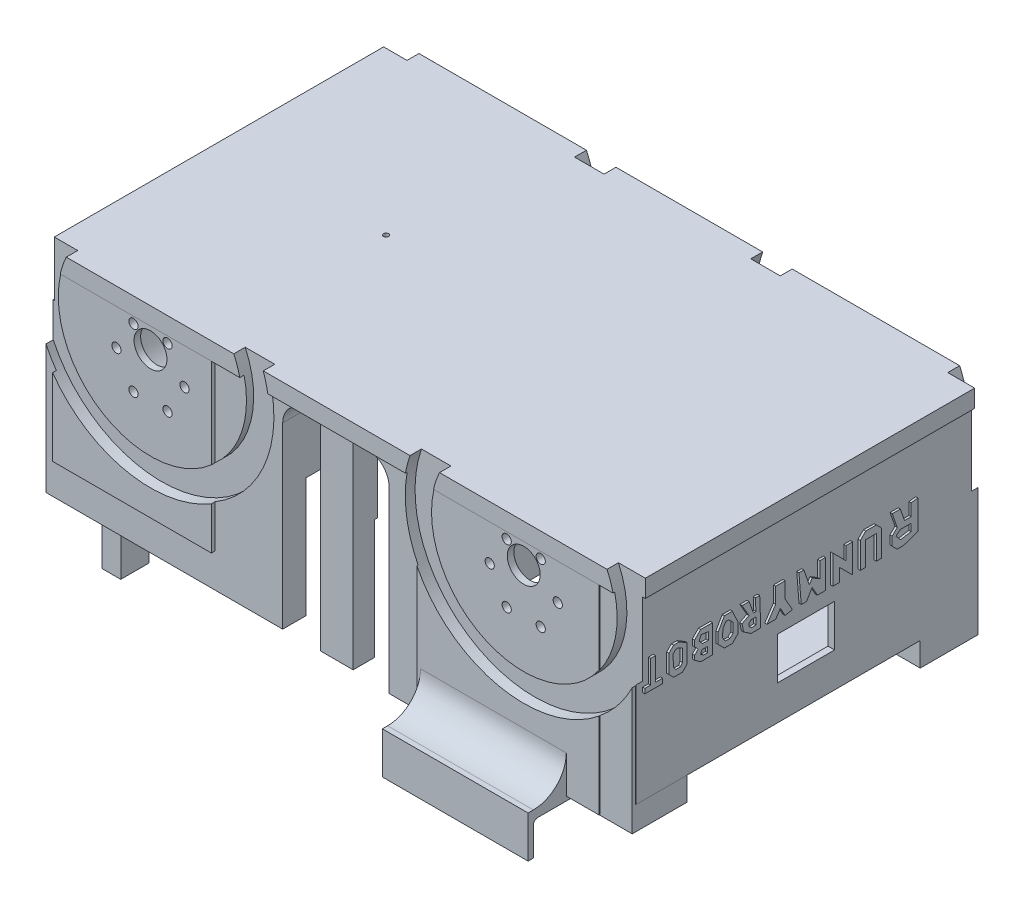
SolidWorks part; units mm, degrees
ref_plane "Front Plane" through (0, 0, 0) normal (0, 0, 1) x (1, 0, 0)
ref_plane "Top Plane" through (0, 0, 0) normal (0, 1, 0) x (1, 0, 0)
ref_plane "Right Plane" through (0, 0, 0) normal (1, 0, 0) x (0, 0, -1)
sketch "MotorHoldersSketch" plane through (0, 0, 0) normal (0, 0, 1) x (1, 0, 0)
  line L0 (0, 0) -> (170, 0) construction
  line L1 (0, 0) -> (0, 23.41) construction
  line L2 (170, 0) -> (170, 23.41) construction
  circle A0 centre (0, 0) radius 23.41
  circle A1 centre (170, 0) radius 23.41
ref_axis "MotorCenterAxis1" through (0, 0, 0) along (0, 0, 1)
ref_axis "MotorCenterAxis2" through (170, 0, 0) along (0, 0, 1)
extrude "MotorHolders" add sketch "MotorHoldersSketch" along normal blind 80 and the other way blind 80
sketch "Sketch3" plane through (0, 0, 0) normal (0, 0, 1) x (1, 0, 0)
  line L1 (1.9406, 21.133) -> (168.3435, 21.133)
  line L2 (1.9406, 21.133) -> (1.9406, 18.3155)
  line L3 (1.9406, 18.3155) -> (168.3435, 18.3155)
  line L4 (168.3435, 21.133) -> (168.3435, 18.3155)
sketch "Sketch4" plane through (0, 0, 0) normal (0, 1, 0) x (1, 0, 0)
  line L1 (221.2811, -76.3794) -> (-41.4939, -76.3794)
  line L2 (221.2811, -76.3794) -> (221.2811, 76.7331)
  line L3 (221.2811, 76.7331) -> (-41.4939, 76.7331)
  line L4 (-41.4939, -76.3794) -> (-41.4939, 76.7331)
extrude "Cut-Extrude1" cut sketch "Sketch4" against normal blind 26
ref_axis "Axis3" through (170, 0, 0) along (0, -1, 0)
sketch3d "ReferencePlanePosition"
  line L0 (170, 0, 0) -> (170, -34.8293, 0)
  line L1 (170, 0, 0) -> (170, -38.994, 0) construction
ref_plane "ReferencePlane" through (170, -34.8293, 0) normal (0, -1, 0) x (-1, 0, 0)
sketch "Sketch6" plane through (170, -34.8293, 0) normal (0, -1, 0) x (-1, 0, 0)
  line L1 (219.5858, 78.949) -> (112.1002, 78.949)
  line L2 (219.5858, 78.949) -> (219.5858, 65.5282)
  line L3 (219.5858, 65.5282) -> (112.1002, 65.5282)
  line L4 (112.1002, 78.949) -> (112.1002, 65.5282)
  line L5 (219.3147, -40.0209) -> (111.499, -40.0209)
  line L6 (219.3147, -40.0209) -> (219.3147, -78.2822)
  line L7 (219.3147, -78.2822) -> (111.499, -78.2822)
  line L8 (111.499, -40.0209) -> (111.499, -78.2822)
  line L9 (61.4891, 77.8627) -> (19.9904, 77.8627)
  line L10 (61.4891, 77.8627) -> (61.4891, 40.7512)
  line L11 (61.4891, 40.7512) -> (19.9904, 40.7512)
  line L12 (19.9904, 77.8627) -> (19.9904, 40.7512)
  line L13 (61.8484, -44.1716) -> (20.0852, -44.1716)
  line L14 (61.8484, -44.1716) -> (61.8484, -79.4437)
  line L15 (61.8484, -79.4437) -> (20.0852, -79.4437)
  line L16 (20.0852, -44.1716) -> (20.0852, -79.4437)
  line L17 (213.765, 73.0364) -> (192.9548, 73.0364)
  line L18 (213.765, 73.0364) -> (213.765, 71.0153)
  line L19 (213.765, 71.0153) -> (192.9548, 71.0153)
  line L20 (192.9548, 73.0364) -> (192.9548, 71.0153)
  line L21 (41.3552, 69.1777) -> (28.5109, 69.1777)
  line L22 (41.3552, 69.1777) -> (41.3552, 50.8413)
  line L23 (41.3552, 50.8413) -> (28.5109, 50.8413)
  line L24 (28.5109, 69.1777) -> (28.5109, 50.8413)
  line L25 (43.3068, -72.8101) -> (32.1723, -72.8101)
  line L26 (43.3068, -72.8101) -> (43.3068, -54.7747)
  line L27 (43.3068, -54.7747) -> (32.1723, -54.7747)
  line L28 (32.1723, -72.8101) -> (32.1723, -54.7747)
  line L29 (211.9411, -70.4881) -> (201.0982, -70.4881)
  line L30 (211.9411, -70.4881) -> (211.9411, -60.1404)
  line L31 (211.9411, -60.1404) -> (201.0982, -60.1404)
  line L32 (201.0982, -70.4881) -> (201.0982, -60.1404)
  line L33 (97.1795, 78.949) -> (79.4162, 78.949)
  line L34 (97.1795, 78.949) -> (97.1795, 67.7632)
  line L35 (97.1795, 67.7632) -> (79.4162, 67.7632)
  line L36 (79.4162, 78.949) -> (79.4162, 67.7632)
  line L37 (58.6711, 51.3198) -> (53.8697, 51.3198)
  line L38 (58.6711, 51.3198) -> (58.6711, 67.7632)
  line L39 (58.6711, 67.7632) -> (53.8697, 67.7632)
  line L40 (53.8697, 51.3198) -> (53.8697, 67.7632)
  line L41 (94.2281, -78.2822) -> (79.4162, -78.2822)
  line L42 (94.2281, -78.2822) -> (94.2281, -67.2515)
  line L43 (94.2281, -67.2515) -> (79.4162, -67.2515)
  line L44 (79.4162, -78.2822) -> (79.4162, -67.2515)
  line L45 (56.3648, -69.8638) -> (51.7107, -69.8638)
  line L46 (56.3648, -69.8638) -> (56.3648, -55.4273)
  line L47 (56.3648, -55.4273) -> (51.7107, -55.4273)
  line L48 (51.7107, -69.8638) -> (51.7107, -55.4273)
  line L49 (-20.7001, -79.4437) -> (-48.8506, -79.4437)
  line L50 (-20.7001, -79.4437) -> (-20.7001, -54.5097)
  line L51 (-20.7001, -54.5097) -> (-48.8506, -54.5097)
  line L52 (-48.8506, -79.4437) -> (-48.8506, -54.5097)
  line L53 (-18.3873, 77.8627) -> (-49.0581, 77.8627)
  line L54 (-18.3873, 77.8627) -> (-18.3873, 51.5325)
  line L55 (-18.3873, 51.5325) -> (-49.0581, 51.5325)
  line L56 (-49.0581, 77.8627) -> (-49.0581, 51.5325)
  line L57 (-41.8141, -72.8101) -> (-31.6362, -72.8101)
  line L58 (-41.8141, -72.8101) -> (-41.8141, -62.9794)
  line L59 (-41.8141, -62.9794) -> (-31.6362, -62.9794)
  line L60 (-31.6362, -72.8101) -> (-31.6362, -62.9794)
  line L61 (-31.6362, 69.1777) -> (-41.5347, 69.1777)
  line L62 (-31.6362, 69.1777) -> (-31.6362, 58.5421)
  line L63 (-31.6362, 58.5421) -> (-41.5347, 58.5421)
  line L64 (-41.5347, 69.1777) -> (-41.5347, 58.5421)
extrude "PowerBankHolders" add sketch "Sketch6" along normal blind 40 and the other way blind 59 separate body
sketch3d "3DSketch3"
  line L0 (170, 0, 0) -> (170, -64.5, 0) construction
ref_plane "Plane2" through (170, -64.5, 0) normal (0, -1, 0) x (-1, 0, 0)
sketch "Sketch7" plane through (170, -64.5, 0) normal (0, -1, 0) x (-1, 0, 0)
  line L1 (-9.5047, -80.801) -> (181.32, -80.801)
  line L2 (-9.5047, -80.801) -> (-9.5047, 73.8662)
  line L3 (-9.5047, 73.8662) -> (181.32, 73.8662)
  line L4 (181.32, -80.801) -> (181.32, 73.8662)
  line L5 (151.8712, -54.3972) -> (26.5361, -54.3972)
  line L6 (151.8712, -54.3972) -> (151.8712, 46.2413)
  line L7 (151.8712, 46.2413) -> (26.5361, 46.2413)
  line L8 (26.5361, -54.3972) -> (26.5361, 46.2413)
ref_point "Point1"
ref_point "Point2"
sketch3d "3DSketch11"
  line L0 (0, 0, -80) -> (170, 0, 80) construction
  point P4 (85, 0, 0)
sketch "MotorHolderExtrudeSketch" plane through (0, 0, 0) normal (0, 0, 1) x (1, 0, 0)
  circle A0 centre (170, 0) radius 20.415
  circle A1 centre (0, 0) radius 20.415
  circle A3 centre (0, 0) radius 23.41 construction
  circle A4 centre (170, 0) radius 23.41 construction
ref_point "TopOfMotors"
ref_plane "TangentToTopOfMotors" through (0, -20.415, 0) normal (0, 1, 0) x (1, 0, 0)
ref_axis "Axis4" through (85, 0, 0) along (0, -1, 0)
ref_plane "BottomOfPowerBankRegion" through (0, -20.425, 0) normal (0, 1, 0) x (1, 0, 0)
ref_point "CenterAtBottomOfPowerBank"
ref_plane "TopOfPowerBankPlane" through (0, -54.425, 0) normal (0, 1, 0) x (1, 0, 0)
sketch "Sketch13" plane through (0, -54.425, 0) normal (0, 1, 0) x (1, 0, 0)
  line L1 (-19.4498, 72.5454) -> (166.1636, 72.5454)
  line L2 (-19.4498, 72.5454) -> (-19.4498, -78.2051)
  line L3 (-19.4498, -78.2051) -> (166.1636, -78.2051)
  line L4 (166.1636, 72.5454) -> (166.1636, -78.2051)
  line L5 (19.3173, -49.583) -> (137.9607, -49.583)
  line L6 (19.3173, -49.583) -> (19.3173, -21.0549)
  line L7 (19.3173, -21.0549) -> (137.9607, -21.0549)
  line L8 (137.9607, -49.583) -> (137.9607, -21.0549)
  line L9 (19.3173, 56.6778) -> (137.9607, 56.6778)
  line L10 (19.3173, 56.6778) -> (19.3173, 36.3234)
  line L11 (19.3173, 36.3234) -> (137.9607, 36.3234)
  line L12 (137.9607, 56.6778) -> (137.9607, 36.3234)
  line L13 (19.3173, 18.3186) -> (137.9607, 18.3186)
  line L14 (19.3173, 18.3186) -> (19.3173, -7.3615)
  line L15 (19.3173, -7.3615) -> (137.9607, -7.3615)
  line L16 (137.9607, 18.3186) -> (137.9607, -7.3615)
sketch "Sketch15" plane through (150.0096, 0, 0) normal (1, 0, 0) x (0, 0, -1)
  line L1 (72.5313, -25.7765) -> (45.7099, -25.7765)
  line L2 (72.5313, -25.7765) -> (72.5313, -24.2242)
  line L3 (72.5313, -24.2242) -> (45.7099, -24.2242)
  line L4 (45.7099, -25.7765) -> (45.7099, -24.2242)
ref_plane "Plane6" through (0, 0, 0) normal (0, 0, 1) x (1, 0, 0)
sketch "MotorGeometry1" plane through (0, 0, 0) normal (0, 0, 1) x (1, 0, 0)
  line L0 (170, 0) -> (170, -13.42)
  line L1 (170, 0) -> (170, -34.8293) construction
  line L2 (170, -13.42) -> (162.25, -13.42) construction
  line L3 (170, -13.42) -> (177.75, -13.42) construction
  line L4 (170, -13.42) -> (170, 7) construction
  line L5 (170, 0) -> (185.5, 0) construction
  line L6 (170, 0) -> (154.5, 0) construction
  line L7 (170, 0) -> (170, 13.42) construction
  line L8 (170, 0) -> (170, 23.41) construction
  line L9 (170, 13.42) -> (177.75, 13.42) construction
  line L10 (170, 13.42) -> (162.25, 13.42)
ref_axis "BoltAxisA" through (185.5, 0, 0) along (0, 0, 1)
ref_axis "BoltAxisB" through (177.75, -13.42, 0) along (0, 0, 1)
ref_axis "BoltAxisC" through (162.25, -13.42, 0) along (0, 0, 1)
ref_axis "BoltAxisD" through (154.5, 0, 0) along (0, 0, 1)
ref_axis "BoltAxisE" through (162.25, 13.42, 0) along (0, 0, 1)
ref_axis "BoltAxisF" through (177.75, 13.42, 0) along (0, 0, 1)
ref_point "Point6"
ref_point "Point7"
ref_point "Point8"
ref_point "Point9"
ref_point "Point10"
ref_point "Point11"
ref_point "Point12"
ref_point "Point13"
ref_point "Point14"
ref_point "Point15"
ref_point "Point16"
ref_point "Point17"
ref_plane "Plane7" through (0, 0, 0) normal (0, 0, 1) x (1, 0, 0)
sketch "MotorGeometry2" plane through (0, 0, 0) normal (0, 0, 1) x (1, 0, 0)
  line L0 (0, 0) -> (0, -13.42) construction
  line L1 (0, -13.42) -> (7.75, -13.42) construction
  line L2 (0, -13.42) -> (-7.75, -13.42) construction
  line L3 (0, 0) -> (0, 13.42)
  line L4 (0, -13.42) -> (0, 7) construction
  line L5 (0, 13.42) -> (7.75, 13.42) construction
  line L6 (0, 13.42) -> (-7.75, 13.42) construction
  line L7 (0, 0) -> (15.5, 0) construction
  line L8 (0, 0) -> (-15.5, 0) construction
  line L9 (0, 0) -> (0, 23.41) construction
ref_axis "Axis11" through (15.5, 0, 0) along (0, 0, 1)
ref_axis "Axis12" through (7.75, 13.42, 0) along (0, 0, 1)
ref_axis "Axis13" through (-7.75, 13.42, 0) along (0, 0, 1)
ref_axis "Axis14" through (-15.5, 0, 0) along (0, 0, 1)
ref_axis "Axis15" through (-7.75, -13.42, 0) along (0, 0, 1)
ref_axis "Axis16" through (7.75, -13.42, 0) along (0, 0, 1)
ref_point "Point18"
ref_point "Point19"
ref_point "Point20"
ref_point "Point21"
ref_point "Point22"
ref_point "Point23"
ref_point "Point24"
ref_point "Point25"
ref_point "Point26"
ref_point "Point27"
ref_point "Point28"
ref_point "Point29"
ref_plane "BottomPlane" through (0, 19.575, 0) normal (0, 1, 0) x (1, 0, 0)
ref_axis "OutputShaftReference1" through (0, 7, 0) along (0, 0, 1)
ref_point "Point35"
ref_axis "OutputShaftReference2" through (170, 7, 0) along (0, 0, 1)
sketch "Sketch21" plane through (0, 19.575, 0) normal (0, 1, 0) x (1, 0, 0)
  line L0 (219.6842, -79.5488) -> (-50.341, -79.5488) construction
  line L1 (-50.341, -79.5488) -> (-50.341, 79.7899) construction
  line L2 (-50.341, 79.7899) -> (219.6842, 79.7899) construction
  line L3 (219.6842, 79.7899) -> (219.6842, -79.5488) construction
  circle A0 centre (85, 0) radius 156.3953
extrude "BottomPlate" add sketch "Sketch21" along normal blind 5 and the other way blind 3
ref_plane "HoleReferencePlane1" through (0, 0, 80) normal (0, 0, 1) x (1, 0, 0)
ref_point "OutputShaftPosition3"
ref_point "OutputShaftPosition1"
sketch "Sketch23" plane through (0, 0, 80) normal (0, 0, 1) x (1, 0, 0)
  line L1 (27.7411, -59.3229) -> (-44.5901, -59.3229)
  line L2 (27.7411, -59.3229) -> (27.7411, 21.8402)
  line L3 (27.7411, 21.8402) -> (-44.5901, 21.8402)
  line L4 (-44.5901, -59.3229) -> (-44.5901, 21.8402)
  line L5 (121.3218, 21.8402) -> (204.258, 21.8402)
  line L6 (121.3218, 21.8402) -> (121.3218, -74.371)
  line L7 (121.3218, -74.371) -> (204.258, -74.371)
  line L8 (204.258, 21.8402) -> (204.258, -74.371)
extrude "MotorMountingSupport1" add sketch "Sketch23" against normal blind 6
ref_plane "HoleReferencePlane2" through (0, 0, -80) normal (0, 0, -1) x (-1, 0, 0)
ref_point "OutputShaftPosition4"
ref_point "OutputShaftPosition2"
sketch "Sketch24" plane through (0, 0, -80) normal (0, 0, -1) x (-1, 0, 0)
  line L1 (-202.1905, -75.2023) -> (-123.8485, -75.2023)
  line L2 (-202.1905, -75.2023) -> (-202.1905, 19.2374)
  line L3 (-202.1905, 19.2374) -> (-123.8485, 19.2374)
  line L4 (-123.8485, -75.2023) -> (-123.8485, 19.2374)
  line L5 (-24.3642, -64.1521) -> (29.5505, -64.1521)
  line L6 (-24.3642, -64.1521) -> (-24.3642, 22.5226)
  line L7 (-24.3642, 22.5226) -> (29.5505, 22.5226)
  line L8 (29.5505, -64.1521) -> (29.5505, 22.5226)
extrude "MotorMountingSuppor2" add sketch "Sketch24" against normal blind 6
sketch "Sketch17" plane through (0, 0, 80) normal (0, 0, 1) x (1, 0, 0)
  circle A0 centre (185.5, 0) radius 2.1
  circle A1 centre (177.75, -13.42) radius 2.1
  circle A2 centre (162.25, -13.42) radius 2.1
  circle A3 centre (154.5, 0) radius 2.1
  circle A4 centre (162.25, 13.42) radius 2.1
  circle A5 centre (177.75, 13.42) radius 2.1
  circle A6 centre (170, 7) radius 7.5
extrude "MotorHoles1" cut sketch "Sketch17" against normal blind 31.5
sketch "Sketch19" plane through (0, 0, -80) normal (0, 0, -1) x (-1, 0, 0)
  circle A0 centre (-185.5, 0) radius 2.1
  circle A1 centre (-177.75, -13.42) radius 2.1
  circle A2 centre (-162.25, -13.42) radius 2.1
  circle A3 centre (-154.5, 0) radius 2.1
  circle A4 centre (-162.25, 13.42) radius 2.1
  circle A5 centre (-177.75, 13.42) radius 2.1
  circle A6 centre (-170, 7) radius 7.5
sketch "BoltHolesSketch3" plane through (0, 0, 80) normal (0, 0, 1) x (1, 0, 0)
  circle A0 centre (7.75, -13.42) radius 2.1
  circle A1 centre (15.5, 0) radius 2.1
  circle A2 centre (7.75, 13.42) radius 2.1
  circle A3 centre (-7.75, 13.42) radius 2.1
  circle A4 centre (-15.5, 0) radius 2.1
  circle A5 centre (-7.75, -13.42) radius 2.1
  circle A6 centre (0, 7) radius 7.5
extrude "Cut-Extrude4" cut sketch "Sketch19" against normal blind 30
extrude "MotorHoles3" cut sketch "BoltHolesSketch3" against normal blind 31.5
sketch "BoltHolesSketch4" plane through (0, 0, -80) normal (0, 0, -1) x (-1, 0, 0)
  circle A0 centre (-15.5, 0) radius 2.1
  circle A1 centre (-7.75, 13.42) radius 2.1
  circle A2 centre (7.75, 13.42) radius 2.1
  circle A3 centre (15.5, 0) radius 2.1
  circle A4 centre (7.75, -13.42) radius 2.1
  circle A5 centre (-7.75, -13.42) radius 2.1
  circle A6 centre (0, 7) radius 7.5
extrude "MotorHoles4" cut sketch "BoltHolesSketch4" against normal blind 15
ref_plane "Front" through (219.0581, 0, 0) normal (1, 0, 0) x (0, 0, -1)
sketch "Sketch29" plane through (219.0581, 0, 0) normal (1, 0, 0) x (0, 0, -1)
  line L1 (76.6955, -63.9254) -> (-77.9397, -63.9254)
  line L2 (76.6955, -63.9254) -> (76.6955, 20.2062)
  line L3 (76.6955, 20.2062) -> (-77.9397, 20.2062)
  line L4 (-77.9397, -63.9254) -> (-77.9397, 20.2062)
  line L5 (-13.4507, -48.1531) -> (12.5493, -48.1531)
  line L6 (-13.4507, -48.1531) -> (-13.4507, -28.9404)
  line L7 (-13.4507, -28.9404) -> (12.5493, -28.9404)
  line L8 (12.5493, -48.1531) -> (12.5493, -28.9404)
extrude "Boss-Extrude8" add sketch "Sketch29" against normal blind 3
ref_plane "RaspberryPiBasePlane" through (0, 16.575, 0) normal (0, -1, 0) x (-1, 0, 0)
sketch "Sketch27" plane through (0, 16.575, 0) normal (0, -1, 0) x (-1, 0, 0)
  line L1 (31.6337, 64.5517) -> (-194.8264, 64.5517)
  line L2 (31.6337, 64.5517) -> (31.6337, -65.4335)
  line L3 (31.6337, -65.4335) -> (-194.8264, -65.4335)
  line L4 (-194.8264, 64.5517) -> (-194.8264, -65.4335)
extrude "Boss-Extrude6" add sketch "Sketch27" against normal blind 3
ref_plane "Plane12" through (0, -74.8293, 0) normal (0, -1, 0) x (-1, 0, 0)
sketch "Sketch28" plane through (0, -74.8293, 0) normal (0, -1, 0) x (-1, 0, 0)
  line L1 (-189.3897, -97.3973) -> (-123.0026, -97.3973)
  line L2 (-189.3897, -97.3973) -> (-189.3897, 96.7192)
  line L3 (-189.3897, 96.7192) -> (-123.0026, 96.7192)
  line L4 (-123.0026, -97.3973) -> (-123.0026, 96.7192)
extrude "CellPhonePlate" add sketch "Sketch28" along normal blind 1.5 and the other way blind 2.5
sketch "Sketch40" plane through (0, 16.575, 0) normal (0, -1, 0) x (1, 0, 0)
  line L1 (-49.5858, -65.5282) -> (-15.7443, -65.5282)
  line L2 (-49.5858, -65.5282) -> (-49.5858, -33.9964)
  line L3 (-49.5858, -33.9964) -> (-15.7443, -33.9964)
  line L4 (-15.7443, -65.5282) -> (-15.7443, -33.9964)
extrude "Boss-Extrude11" add sketch "Sketch40" along normal blind 40
fillet "Fillet2" radius 15 1 edges at (-33.0588, 16.575, -33.9964) type face fillet first side face at (-28.7089, -2.1691, -33.9964) second side face at (85, 16.575, 156.3953)
fillet "Fillet3" radius 15 1 edges at (-32.6651, -23.425, -65.5282) type face fillet first side face at (-5.65, -13.42, -65.5282) second side face at (-32.6651, -23.425, -49.7623)
sketch "Sketch11" plane through (0, -20.425, 0) normal (0, 1, 0) x (1, 0, 0)
  line L0 (-34.2162, 4.2922) -> (204.2162, -4.2922) construction
  line L5 (-34.2162, -64.7581) -> (-34.2162, 73.3425)
  line L6 (204.2162, 63.611) -> (204.2162, -72.1954)
  line L7 (204.2162, -72.1954) -> (-34.2162, -64.7581)
  line L8 (204.2162, 63.611) -> (-34.2162, 73.3425)
  circle A0 centre (85, 0) radius 104 construction
extrude "PowerBankCut" cut sketch "Sketch11" against normal up to surface (54.4043 mm away) up to face at (204.7754, -74.8293, 66.9767)
extrude "MotorHolderCut" cut sketch "MotorHolderExtrudeSketch" against normal blind 77 and the other way blind 77
sketch "Sketch31" plane through (219.0581, 0, 0) normal (1, 0, 0) x (0, 0, -1)
  line L0 (49.4417, -6.1927) -> (49.4417, -19.3739)
  line L1 (49.4417, -19.3739) -> (42.9342, -21.6341)
  line L2 (42.9342, -21.6341) -> (40.0618, -21.6341)
  line L3 (40.0618, -21.6341) -> (37.7863, -19.3586)
  line L4 (37.7863, -19.3586) -> (37.7863, -15.3813)
  line L5 (37.7863, -15.3813) -> (40.0618, -13.1059)
  line L6 (40.0618, -13.1059) -> (37.7863, -6.5545)
  line L7 (37.7863, -6.5545) -> (41.498, -6.5545)
  line L8 (41.498, -6.5545) -> (43.4004, -12.0319)
  line L9 (43.4004, -12.0319) -> (46.389, -12.0319)
  line L10 (46.389, -12.0319) -> (46.389, -6.5545)
  line L11 (46.389, -6.5545) -> (49.4417, -6.1927)
  line L12 (33.0193, -21.6341) -> (33.0193, -9.8302)
  line L13 (33.0193, -9.8302) -> (30.5402, -7.3511)
  line L14 (30.5402, -7.3511) -> (25.7203, -7.3511)
  line L15 (25.7203, -7.3511) -> (23.2412, -9.8302)
  line L16 (23.2412, -9.8302) -> (23.2412, -21.6341)
  line L17 (23.2412, -21.6341) -> (25.7203, -21.6341)
  line L18 (25.7203, -21.6341) -> (25.7203, -10.7454)
  line L19 (25.7203, -10.7454) -> (30.5402, -10.7454)
  line L20 (30.5402, -10.7454) -> (30.5402, -21.6341)
  line L21 (30.5402, -21.6341) -> (33.0193, -21.6341)
  line L22 (19.7226, -8.5907) -> (19.7226, -21.6341)
  line L23 (19.7226, -21.6341) -> (13.8207, -15.7322)
  line L24 (13.8207, -15.7322) -> (13.8207, -21.6341)
  line L25 (13.8207, -21.6341) -> (10.7708, -21.6341)
  line L26 (10.7708, -21.6341) -> (10.7708, -8.5907)
  line L27 (10.7708, -8.5907) -> (16.7716, -14.5915)
  line L28 (16.7716, -14.5915) -> (16.7716, -8.5907)
  line L29 (16.7716, -8.5907) -> (19.7226, -8.5907)
  line L30 (7.3891, -8.5907) -> (7.3891, -21.6341)
  line L31 (7.3891, -21.6341) -> (3.7282, -21.6341)
  line L32 (3.7282, -21.6341) -> (1.3209, -17.37)
  line L33 (1.3209, -17.37) -> (-1.2519, -21.6341)
  line L34 (-1.2519, -21.6341) -> (-3.6554, -21.6341)
  line L35 (-3.6554, -21.6341) -> (-4.6916, -8.5907)
  line L36 (-4.6916, -8.5907) -> (-2.4537, -8.5907)
  line L37 (-2.4537, -8.5907) -> (0.0345, -15.7545)
  line L38 (0.0345, -15.7545) -> (1.3209, -13.6224)
  line L39 (1.3209, -13.6224) -> (4.8544, -15.7545)
  line L40 (4.8544, -15.7545) -> (4.8544, -8.5907)
  line L41 (4.8544, -8.5907) -> (7.3891, -8.5907)
  line L42 (-7.6823, -21.6341) -> (-10.9875, -15.7545)
  line L43 (-10.9875, -15.7545) -> (-10.9875, -8.5907)
  line L44 (-10.9875, -8.5907) -> (-15.3102, -8.5907)
  line L45 (-15.3102, -8.5907) -> (-15.3102, -15.7545)
  line L46 (-15.3102, -15.7545) -> (-19.2695, -21.6341)
  line L47 (-19.2695, -21.6341) -> (-15.3102, -21.6341)
  line L48 (-15.3102, -21.6341) -> (-13.1489, -18.4245)
  line L49 (-13.1489, -18.4245) -> (-10.9875, -22.2693)
  line L50 (-10.9875, -22.2693) -> (-7.6823, -21.6341)
  line L51 (46.389, -17.8857) -> (46.389, -14.5915)
  line L52 (46.389, -14.5915) -> (41.498, -14.5915)
  line L53 (41.498, -14.5915) -> (39.5067, -16.2541)
  line L54 (39.5067, -16.2541) -> (41.5656, -18.7201)
  line L55 (41.5656, -18.7201) -> (46.389, -17.8857)
  line L56 (-22.571, -8.5907) -> (-22.0989, -21.6341)
  line L57 (-22.0989, -21.6341) -> (-26.4915, -21.6341)
  line L58 (-26.4915, -21.6341) -> (-29.9116, -19.3586)
  line L59 (-29.9116, -19.3586) -> (-30.636, -15.7545)
  line L60 (-30.636, -15.7545) -> (-27.4135, -14.1052)
  line L61 (-27.4135, -14.1052) -> (-30.636, -8.5907)
  line L62 (-30.636, -8.5907) -> (-27.4135, -8.5907)
  line L63 (-27.4135, -8.5907) -> (-25.3987, -14.1052)
  line L64 (-25.3987, -14.1052) -> (-24.2952, -14.1052)
  line L65 (-24.2952, -14.1052) -> (-24.4948, -8.5907)
  line L66 (-24.4948, -8.5907) -> (-22.571, -8.5907)
  line L67 (-35.0099, -8.5907) -> (-38.6395, -8.5907)
  line L68 (-38.6395, -8.5907) -> (-41.5241, -13.6224)
  line L69 (-41.5241, -13.6224) -> (-41.5241, -18.4245)
  line L70 (-41.5241, -18.4245) -> (-38.6395, -21.3091)
  line L71 (-38.6395, -21.3091) -> (-35.0099, -21.3091)
  line L72 (-35.0099, -21.3091) -> (-32.4978, -18.797)
  line L73 (-32.4978, -18.797) -> (-32.4978, -14.1052)
  line L74 (-32.4978, -14.1052) -> (-35.0099, -8.5907)
  line L75 (-44.0593, -21.3091) -> (-44.0593, -8.5907)
  line L76 (-44.0593, -8.5907) -> (-49.4499, -8.5907)
  line L77 (-49.4499, -8.5907) -> (-52.2269, -11.3677)
  line L78 (-52.2269, -11.3677) -> (-52.2269, -14.1052)
  line L79 (-52.2269, -14.1052) -> (-50.5777, -15.7545)
  line L80 (-50.5777, -15.7545) -> (-52.2269, -17.4037)
  line L81 (-52.2269, -17.4037) -> (-52.2269, -19.3586)
  line L82 (-52.2269, -19.3586) -> (-49.4499, -21.3091)
  line L83 (-49.4499, -21.3091) -> (-44.0593, -21.3091)
  line L84 (-57.7977, -21.3091) -> (-55.6011, -19.1125)
  line L85 (-55.6011, -19.1125) -> (-55.6011, -10.7454)
  line L86 (-55.6011, -10.7454) -> (-59.2637, -8.5907)
  line L87 (-59.2637, -8.5907) -> (-61.7818, -8.5907)
  line L88 (-61.7818, -8.5907) -> (-63.9365, -10.7454)
  line L89 (-63.9365, -10.7454) -> (-63.9365, -19.1125)
  line L90 (-63.9365, -19.1125) -> (-61.7818, -21.2672)
  line L91 (-61.7818, -21.2672) -> (-57.7977, -21.3091)
  line L92 (-66.7918, -21.2672) -> (-74.8705, -21.2672)
  line L93 (-74.8705, -21.2672) -> (-74.8705, -19.1125)
  line L94 (-74.8705, -19.1125) -> (-72.2665, -19.1125)
  line L95 (-72.2665, -19.1125) -> (-72.2665, -8.5907)
  line L96 (-72.2665, -8.5907) -> (-69.9977, -8.5907)
  line L97 (-69.9977, -8.5907) -> (-69.9977, -19.1125)
  line L98 (-69.9977, -19.1125) -> (-66.7918, -19.1125)
  line L99 (-66.7918, -19.1125) -> (-66.7918, -21.2672)
  line L100 (-36.1114, -18.797) -> (-34.7181, -17.4037)
  line L101 (-34.7181, -17.4037) -> (-34.7181, -13.1059)
  line L102 (-34.7181, -13.1059) -> (-36.6627, -11.1613)
  line L103 (-36.6627, -11.1613) -> (-37.8659, -11.1613)
  line L104 (-37.8659, -11.1613) -> (-39.3107, -13.1059)
  line L105 (-39.3107, -13.1059) -> (-39.5155, -16.8544)
  line L106 (-39.5155, -16.8544) -> (-38.25, -18.7201)
  line L107 (-38.25, -18.7201) -> (-36.1114, -18.797)
  line L108 (-46.2436, -16.8544) -> (-48.9032, -16.8544)
  line L109 (-48.9032, -16.8544) -> (-49.4499, -18.4245)
  line L110 (-49.4499, -18.4245) -> (-48.0836, -19.3586)
  line L111 (-48.0836, -19.3586) -> (-46.2436, -19.3586)
  line L112 (-46.2436, -19.3586) -> (-46.2436, -16.8544)
  line L113 (-45.9206, -14.5915) -> (-45.9206, -11.1613)
  line L114 (-45.9206, -11.1613) -> (-49.2105, -10.7454)
  line L115 (-49.2105, -10.7454) -> (-50.1756, -12.8764)
  line L116 (-50.1756, -12.8764) -> (-48.5891, -14.5915)
  line L117 (-48.5891, -14.5915) -> (-45.9206, -14.5915)
  line L118 (-58.5672, -18.7201) -> (-57.7977, -17.4037)
  line L119 (-57.7977, -17.4037) -> (-57.7977, -11.7636)
  line L120 (-57.7977, -11.7636) -> (-59.6573, -10.7454)
  line L121 (-59.6573, -10.7454) -> (-60.8144, -10.7454)
  line L122 (-60.8144, -10.7454) -> (-62.101, -12.0319)
  line L123 (-62.101, -12.0319) -> (-61.7818, -17.4037)
  line L124 (-61.7818, -17.4037) -> (-60.8144, -18.7201)
  line L125 (-60.8144, -18.7201) -> (-58.5672, -18.7201)
  line L126 (-24.2952, -19.3586) -> (-24.2952, -16.2541)
  line L127 (-24.2952, -16.2541) -> (-26.4915, -16.2541)
  line L128 (-26.4915, -16.2541) -> (-27.4135, -17.1761)
  line L129 (-27.4135, -17.1761) -> (-27.4135, -18.4245)
  line L130 (-27.4135, -18.4245) -> (-26.3339, -19.5041)
  line L131 (-26.3339, -19.5041) -> (-24.2952, -19.3586)
extrude "Label" add sketch "Sketch31" along normal blind 1
sketch "Sketch32" plane through (0, 19.575, 0) normal (0, 1, 0) x (1, 0, 0)
  line L1 (-48.8137, 80.4301) -> (220.392, 80.4301)
  line L2 (-48.8137, 80.4301) -> (-48.8137, -80.215)
  line L3 (-48.8137, -80.215) -> (220.392, -80.215)
  line L4 (220.392, 80.4301) -> (220.392, -80.215)
  line L5 (283.5566, -218.7268) -> (-136.4889, -218.7268)
  line L8 (-136.4889, -218.7268) -> (-136.4889, 206.3198)
  line L10 (283.5566, 206.3198) -> (283.5566, -218.7268)
  line L13 (283.5566, 206.3198) -> (-136.4889, 206.3198)
extrude "BaseDefiningCut" cut sketch "Sketch32" along normal blind 20 and the other way blind 20
sketch "Sketch39" plane through (0, 16.575, 0) normal (0, -1, 0) x (1, 0, 0)
  line L1 (-48.8137, -65.5282) -> (-16.0867, -65.5282)
  line L2 (-48.8137, -65.5282) -> (-48.8137, -46.28)
  line L3 (-48.8137, -46.28) -> (-16.0867, -46.28)
  line L4 (-16.0867, -65.5282) -> (-16.0867, -46.28)
sketch "Sketch35" plane through (0, 0, -80.4301) normal (0, 0, -1) x (-1, 0, 0)
  line L0 (69.0502, 16.3777) -> (-36.4474, 27.6206)
  line L1 (-36.4474, 27.6206) -> (71.6404, 26.1593)
  line L2 (69.0502, 16.3777) -> (71.6404, 26.1593)
  line L3 (-223.8844, 30.8145) -> (-223.8844, 17.5678)
  line L4 (-223.8844, 17.5678) -> (-116.0163, 30.8145)
  line L5 (-116.0163, 30.8145) -> (-223.8844, 30.8145)
sketch "Sketch36" plane through (-49.3147, 0, 0) normal (-1, 0, 0) x (0, 0, 1)
  line L0 (40.0209, -74.8293) -> (40.0209, -38.3689) construction
  line L1 (49.3822, -38.3689) -> (78.2822, -38.3689) construction
  line L2 (40.0209, -38.3689) -> (40.0209, -74.8293) construction
  line L3 (78.2822, -0.425) -> (78.2822, -74.8293) construction
  circle A1 centre (49.3822, -38.3689) radius 7.7902
extrude "Cut-Extrude6" cut sketch "Sketch36" against normal blind 40
sketch "Sketch37" plane through (0, -20.425, 0) normal (0, -1, 0) x (1, 0, 0)
  line L1 (144.416, -35.6729) -> (89.0759, -35.6729)
  line L2 (144.416, -35.6729) -> (144.416, -65.4438)
  line L3 (144.416, -65.4438) -> (89.0759, -65.4438)
  line L4 (89.0759, -35.6729) -> (89.0759, -65.4438)
extrude "Cut-Extrude7" cut sketch "Sketch37" against normal blind 36
sketch "Sketch38" plane through (0, 16.575, 0) normal (0, -1, 0) x (1, 0, 0)
  line L0 (25.9964, 80.215) -> (25.9964, -1.3165) construction
  line L1 (-48.8137, 80.215) -> (219.2574, 80.215) construction
  circle A0 centre (25.9964, -1.3165) radius 1.1452
extrude "Cut-Extrude8" cut sketch "Sketch38" against normal blind 10
sketch "Sketch41" plane through (0, 0, 80) normal (0, 0, 1) x (1, 0, 0)
  circle A0 centre (0, 7) radius 42
  circle A1 centre (0, 7) radius 54.5
extrude "SpaceForWheel1" cut sketch "Sketch41" against normal blind 5 and the other way blind 10
sketch "Sketch42" plane through (0, 0, 80) normal (0, 0, 1) x (1, 0, 0)
  circle A0 centre (170, 7) radius 42
  circle A1 centre (170, 7) radius 54.5
extrude "Cut-Extrude10" cut sketch "Sketch42" against normal blind 5 and the other way blind 10
sketch "Sketch43" plane through (0, 0, -80) normal (0, 0, -1) x (-1, 0, 0)
  circle A0 centre (-170, 7) radius 42
  circle A1 centre (-170, 7) radius 54.5
extrude "Cut-Extrude11" cut sketch "Sketch43" against normal blind 5 and the other way blind 10
sketch "Sketch44" plane through (0, 0, -80) normal (0, 0, -1) x (-1, 0, 0)
  circle A0 centre (0, 7) radius 42
  circle A1 centre (0, 7) radius 54.5
extrude "Cut-Extrude12" cut sketch "Sketch44" against normal blind 5 and the other way blind 10
sketch "Sketch45" plane through (-48.8137, 0, 0) normal (-1, 0, 0) x (0, 0, 1)
  line L0 (-75, 24.575) -> (75, 24.575) construction
  line L1 (-72.1063, 24.575) -> (42.0312, 24.575)
  line L2 (-72.1063, 24.575) -> (-72.1063, -117.572)
  line L3 (-72.1063, -117.572) -> (42.0312, -117.572)
  line L4 (42.0312, 24.575) -> (42.0312, -117.572)
extrude "BackPlate" add sketch "Sketch45" against normal blind 2
sketch "Sketch46" plane through (0, -74.8293, 0) normal (0, -1, 0) x (1, 0, 0)
  line L1 (97.1427, -74.9256) -> (213.5256, -74.9256)
  line L2 (97.1427, -74.9256) -> (97.1427, -71.5234)
  line L3 (97.1427, -71.5234) -> (213.5256, -71.5234)
  line L4 (213.5256, -74.9256) -> (213.5256, -71.5234)
  line L5 (97.1427, 72.8226) -> (213.5256, 72.8226)
  line L6 (97.1427, 72.8226) -> (97.1427, 77.4687)
  line L7 (97.1427, 77.4687) -> (213.5256, 77.4687)
  line L8 (213.5256, 72.8226) -> (213.5256, 77.4687)
fillet "Fillet4" radius 15 1 edges at (156.1962, -72.3293, 80) type face fillet first side face at (156.1962, -72.3293, 88.6987) second side face at (158.9587, -64.3583, 80)
fillet "Fillet5" radius 15 1 edges at (156.6191, -72.3293, -80) type face fillet first side face at (145.4136, -72.3293, -84.8606) second side face at (171.266, -61.8458, -80)
sketch "Sketch47" plane through (0, -76.3293, 0) normal (0, -1, 0) x (1, 0, 0)
  line L0 (123.0026, 97.3973) -> (123.0026, -96.7192) construction
  line L1 (189.3897, -96.7192) -> (123.0026, -96.7192)
  line L2 (189.3897, -96.7192) -> (189.3897, -93.4402)
  line L3 (189.3897, -93.4402) -> (123.0026, -93.4402)
  line L4 (123.0026, -96.7192) -> (123.0026, -93.4402)
  line L6 (189.3897, 97.3973) -> (123.0026, 97.3973)
  line L7 (189.3897, 97.3973) -> (189.3897, 94.965)
  line L8 (189.3897, 94.965) -> (123.0026, 94.965)
  line L9 (123.0026, 97.3973) -> (123.0026, 94.965)
extrude "Boss-Extrude14" add sketch "Sketch47" along normal blind 15
fillet "Fillet6" radius 2 1 edges at (156.1962, -76.3293, -93.4402) type face fillet first side face at (156.1962, -83.8293, -93.4402) second side face at (156.1962, -76.3293, 0.7624)
fillet "Fillet7" radius 2 1 edges at (156.1962, -76.3293, 94.965) type face fillet first side face at (156.1962, -83.8293, 94.965) second side face at (156.1962, -76.3293, 1.7624)
fillet "Fillet8" radius 10 1 edges at (57.8998, 16.575, -72.2386) type face fillet first side face at (57.8998, -26.2264, -71.3533) second side face at (25.9964, 16.575, -2.4617)
fillet "Fillet9" radius 10 1 edges at (108.5109, 16.575, -59.3069) type face fillet first side face at (108.5109, -15.7761, -62.8937) second side face at (25.9964, 16.575, -2.4617)
fillet "Fillet10" radius 10 1 edges at (108.1516, 16.575, 61.8076) type face fillet first side face at (108.1516, -26.2264, 64.2714) second side face at (25.9964, 16.575, -2.4617)
sketch "Sketch49" plane through (0, 0, 80) normal (0, 0, 1) x (1, 0, 0)
  line L0 (27.7411, -24.5346) -> (27.7411, 16.575) construction
  circle A0 centre (27.7411, 12.953) radius 3.5831
fillet "Fillet11" radius 10 1 edges at (58.501, 16.575, 59.1515) type face fillet first side face at (58.501, -26.2264, 61.9844) second side face at (25.9964, 16.575, -2.4617)
sketch "Sketch50" plane through (0, -74.8293, 0) normal (0, -1, 0) x (1, 0, 0)
  line L1 (-49.3147, 40.0209) -> (-40.7689, 40.0209)
  line L2 (-49.3147, 40.0209) -> (-49.3147, 52.7795)
  line L3 (-49.3147, 52.7795) -> (-40.7689, 52.7795)
  line L4 (-40.7689, 40.0209) -> (-40.7689, 52.7795)
  line L5 (-49.5858, -65.5282) -> (-35.8777, -65.5282)
  line L6 (-49.5858, -65.5282) -> (-49.5858, -77.7316)
  line L7 (-49.5858, -77.7316) -> (-35.8777, -77.7316)
  line L8 (-35.8777, -65.5282) -> (-35.8777, -77.7316)
extrude "Boss-Extrude15" add sketch "Sketch50" along normal up to surface (42.7427 mm away) up to face at (-47.8137, -117.572, -15.0375)
